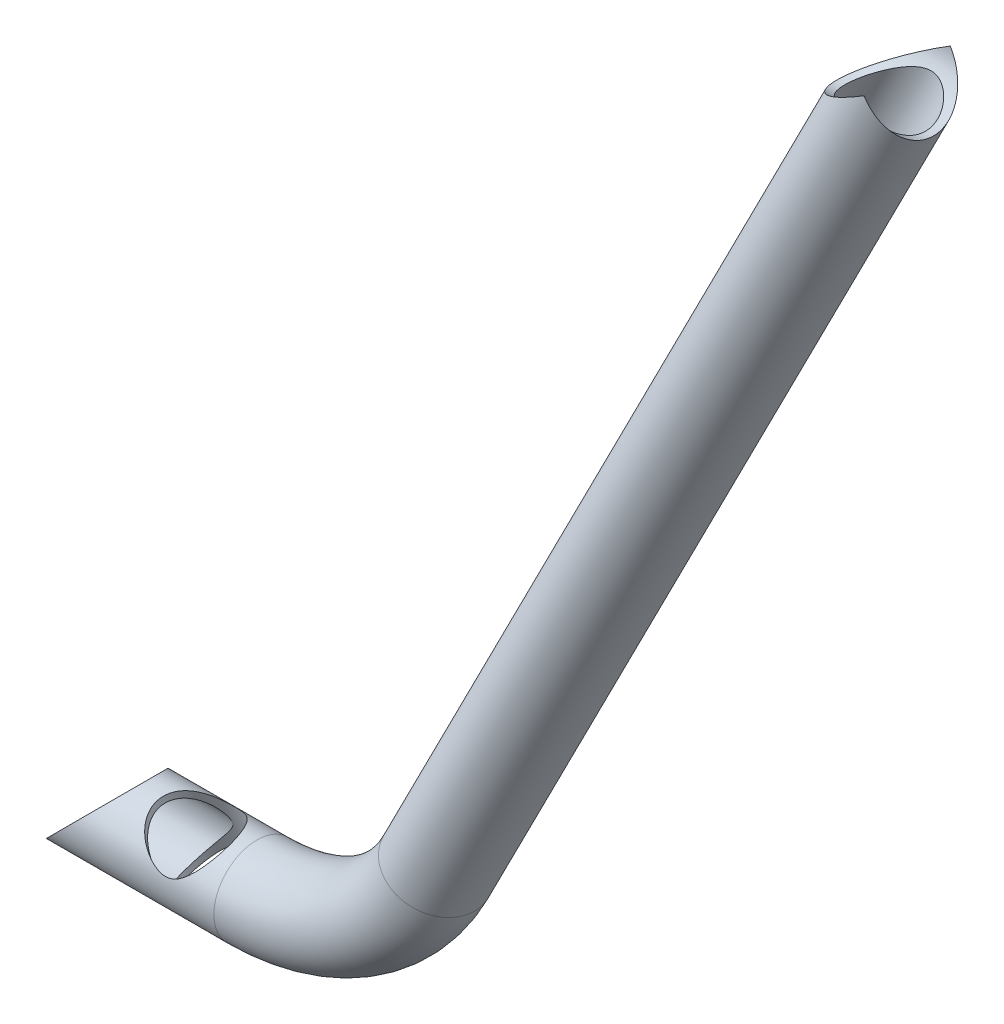
SolidWorks part; units mm, degrees
ref_plane "Front" through (0, 0, 0) normal (0, 0, 1) x (1, 0, 0)
ref_plane "Top" through (0, 0, 0) normal (0, 1, 0) x (1, 0, 0)
ref_plane "Right" through (0, 0, 0) normal (1, 0, 0) x (0, 0, -1)
sketch "Эскиз1" plane through (0, 0, 0) normal (0, 0, 1) x (1, 0, 0)
  line L0 (0, 0) -> (-163.9548, -321.7793)
  line L1 (-226.3252, -360) -> (-293.4292, -360)
  arc A0 (-163.9548, -321.7793) -> (-226.3252, -360) centre (-226.3252, -290) cw
  point P6 (-183.4292, -360)
  dimension "D4" = 70
  dimension "D1" = 110
  dimension "D2" = 63
  dimension "D3" = 360
ref_plane "Плоскость1" through (-293.4292, -360, 0) normal (-1, 0, 0) x (0, 0, 1)
sketch "Эскиз2" plane through (-293.4292, -360, 0) normal (-1, 0, 0) x (0, 0, 1)
  circle A0 centre (0, 0) radius 15
  dimension "D1" = 30
sweep "По траектории1" add profiles "Эскиз2" path "Эскиз1"
sketch "Эскиз3" plane through (-293.4292, 0, 0) normal (-1, 0, 0) x (0, 0, 1)
  circle A0 centre (0, -360) radius 12.5
  circle A1 centre (0, -360) radius 15 construction
  dimension "D1" = 2.5
sweep "Вырез-По траектории1" cut profiles "Эскиз3" path "Эскиз1<2>"
sketch "Эскиз1<2>" plane through (0, 0, 0) normal (0, 0, 1) x (1, 0, 0) same geometry as "Эскиз1"
sketch "Эскиз4" plane through (0, 0, 0) normal (0, 0, 1) x (1, 0, 0)
  line L0 (-263.4292, -345) -> (-293.4292, -375)
  line L1 (-226.3252, -345) -> (-293.4292, -345) construction
  line L2 (-293.4292, -375) -> (-293.4292, -345)
  line L3 (-293.4292, -345) -> (-263.4292, -345)
extrude "Вырез-Вытянуть1" cut sketch "Эскиз4" against normal through all and the other way through all
sketch "Эскиз5" plane through (0, 0, 0) normal (1, 0, 0) x (0, 0, -1)
  line L0 (-15, 0) -> (-15, 6.8099)
  line L1 (-15, 0) -> (-15, -321.7793) construction
  line L2 (15, -321.7793) -> (15, 0) construction
  line L3 (-15, 6.8099) -> (15, 6.8099)
  line L4 (15, 6.8099) -> (15, 0)
  arc A0 (-15, 0) -> (15, 0) centre (0, 0) ccw
  ellipse E1 centre (0, 0) end of major axis (-15, 0) minor radius 6.8099 construction
  dimension "D1" = 15
extrude "Вырез-Вытянуть2" cut sketch "Эскиз5" against normal through all and the other way through all
ref_plane "Плоскость для 20град" through (0, -390, 0) normal (0, 1, 0) x (1, 0, 0)
ref_plane "Плоскость 20град" through (0, -331.9834, -120.8321) normal (0, -0.9397, -0.342) x (1, 0, 0)
sketch "Эскиз8" plane through (0, -331.9834, -120.8321) normal (0, -0.9397, -0.342) x (1, 0, 0)
  line L0 (-293.4292, 138.1273) -> (-293.4292, 108.1273) construction
  line L1 (-226.3252, 138.1273) -> (-283.5595, 138.1273) construction
  circle A0 centre (-243.4292, 123.1273) radius 12.8888
  dimension "D3" = 25.7777
  dimension "D1" = 50
  dimension "D2" = 15
extrude "отверстие под углом" cut sketch "Эскиз8" against normal through all
ref_plane "Плоскость для точки" through (9.192, -15, 0) normal (0.891, -0.454, 0) x (0, 0, -1)
sketch "точка для сборки" plane through (9.192, -15, 0) normal (0.891, -0.454, 0) x (0, 0, -1)
  point P0 (0, 0)
sketch "для сборки" plane through (40.7854, -40.7854, 0) normal (-0.7071, 0.7071, 0) x (0, 0, 1)
  ellipse E1 centre (0, -451.4376) end of major axis (0, -469.1153) minor radius 12.5 construction
  point P0 (0, -451.4376)
